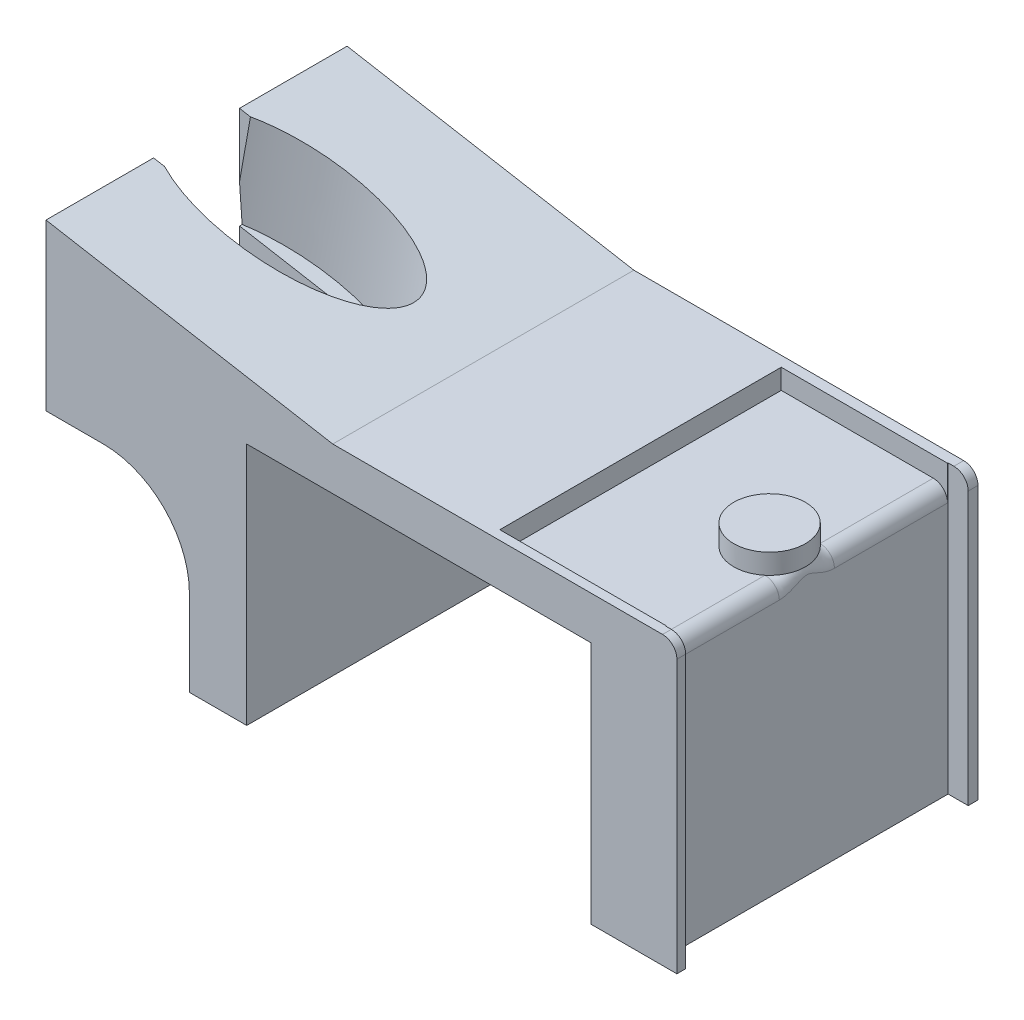
SolidWorks part; units mm, degrees
ref_plane "前视基准面" through (0, 0, 0) normal (0, 0, 1) x (1, 0, 0)
ref_plane "上视基准面" through (0, 0, 0) normal (0, 1, 0) x (1, 0, 0)
ref_plane "右视基准面" through (0, 0, 0) normal (1, 0, 0) x (0, 0, -1)
sketch "草图1" plane through (0, 0, 0) normal (0, 0, 1) x (1, 0, 0)
  line L0 (0, 0) -> (0, 10)
  line L1 (0, 10) -> (-12, 10)
  line L2 (-22, 11.765) -> (-22, 6)
  line L3 (-22, 6) -> (-20, 6)
  line L4 (-17, 3) -> (-17, 0)
  line L5 (-17, 0) -> (-15, 0)
  line L6 (-15, 0) -> (-15, 8.5)
  line L7 (-15, 8.5) -> (-3, 8.5)
  line L8 (-3, 8.5) -> (-3, 0)
  line L9 (-3, 0) -> (0, 0)
  line L11 (-22, 11.765) -> (-22, 11.7672)
  line L12 (-12, 10) -> (-22, 11.765)
  arc A0 (-17, 3) -> (-20, 6) centre (-20, 3) ccw
  dimension "D1" = 3
  dimension "D2" = 12
  dimension "D3" = 3
  dimension "D4" = 2
  dimension "D5" = 10
  dimension "D6" = 8.5
  dimension "D7" = 6
  dimension "D8" = 12
  dimension "D9" = 22
extrude "拉伸1" add sketch "草图1" along normal blind 10.5 contours L2 L3 A0 L4 L5 L6 L7 L8 L9 L0 L1 L12
sketch "草图2" plane through (1.3491, 7.6439, 0) normal (0.1738, 0.9848, 0) x (0.9848, -0.1738, 0)
  line L0 (-23.71, -5.25) -> (-19.2279, -5.25) construction
  line L1 (-23.71, -10.5) -> (-23.71, 0) construction
  line L2 (-19.2279, -3.7519) -> (-24.5549, -3.7519)
  line L3 (-19.2279, -6.7481) -> (-24.5549, -6.7481)
  line L4 (-24.5549, -3.7519) -> (-24.5549, -6.7481)
  arc A0 (-19.2279, -6.7481) -> (-19.2279, -3.7519) centre (-19.2279, -5.25) ccw
extrude "拉伸2" cut sketch "草图2" against normal blind 10.5
sketch "草图3" plane through (1.3491, 7.6439, 0) normal (0.1738, 0.9848, 0) x (0.9848, -0.1738, 0)
  line L0 (-17.7297, -5.25) -> (-24.4777, -5.25) construction
  arc A0 (-19.2279, -6.7481) -> (-19.2279, -3.7519) centre (-19.2279, -5.25) ccw construction
  ellipse E0 centre (-20.3859, -5.25) end of major axis (-24.7479, -5.25) minor radius 2.0266
extrude "拉伸3" cut sketch "草图3" against normal blind 3.5
sketch "草图4" plane through (0, 10, 0) normal (0, 1, 0) x (1, 0, 0)
  line L0 (-0.6748, -5.2679) -> (-6.5488, -5.2679) construction
  line L1 (0, -10.5) -> (0, 0) construction
  line L2 (-6.5, -10.1749) -> (2.5, -10.1749)
  line L3 (-6.5, -10.1749) -> (-6.5, -0.3609)
  line L4 (-6.5, -0.3609) -> (2.5, -0.3609)
  line L5 (2.5, -10.1749) -> (2.5, -0.3609)
  line L6 (-6.5, -10.1749) -> (2.5, -0.3609) construction
  line L7 (-6.5, -0.3609) -> (2.5, -10.1749) construction
  circle A0 centre (-2, -5.2679) radius 1.25
  point P2 (-2, -5.2679)
  dimension "D3" = 2.5
  dimension "D1" = 6.5
  dimension "D2" = 9
extrude "拉伸4" cut sketch "草图4" against normal blind 0.7
sketch "草图5" plane through (0, 0, 0) normal (1, 0, 0) x (0, 0, -1)
  line L0 (-0.3609, 9.3) -> (-10.1749, 9.3) construction
  line L1 (-10.1938, 19.4721) -> (-0.342, 19.4721)
  line L2 (-10.1938, 19.4721) -> (-10.1938, -0.8721)
  line L3 (-10.1938, -0.8721) -> (-0.342, -0.8721)
  line L4 (-0.342, 19.4721) -> (-0.342, -0.8721)
  line L5 (-10.1938, 19.4721) -> (-0.342, -0.8721) construction
  line L6 (-10.1938, -0.8721) -> (-0.342, 19.4721) construction
  point P0 (-5.2679, 9.3)
extrude "拉伸5" cut sketch "草图5" against normal blind 0.7
fillet "圆角1" radius 0.5 1 edges at (-0.7, 9.3, 5.2679)
fillet "圆角2" radius 0.5 1 edges at (0, 10, 0.171)
fillet "圆角3" radius 0.5 1 edges at (0, 10, 10.3469)
